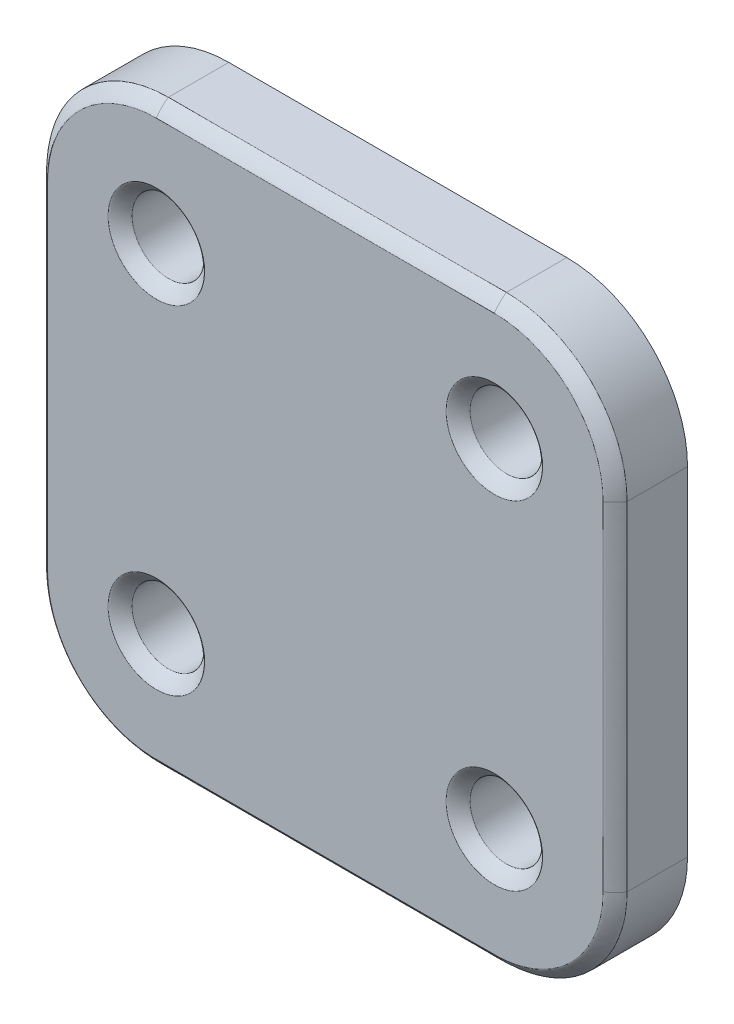
SolidWorks part; units mm, degrees
ref_plane "Plan de face" through (0, 0, 0) normal (0, 0, 1) x (1, 0, 0)
ref_plane "Plan de dessus" through (0, 0, 0) normal (0, 1, 0) x (1, 0, 0)
ref_plane "Plan de droite" through (0, 0, 0) normal (1, 0, 0) x (0, 0, -1)
sketch "Esquisse1" plane through (0, 0, 0) normal (0, 0, 1) x (1, 0, 0)
  line L0 (-7, 7) -> (7, 7) construction
  line L1 (7, -12) -> (-7, -12)
  line L2 (12, -7) -> (12, 7)
  line L3 (7, 12) -> (-7, 12)
  line L4 (-12, -7) -> (-12, 7)
  line L5 (12, -12) -> (-12, 12) construction
  line L6 (12, 12) -> (-12, -12) construction
  line L7 (-7, -7) -> (-7, 7) construction
  arc A0 (-7, -12) -> (-12, -7) centre (-7, -7) cw
  arc A1 (7, -12) -> (12, -7) centre (7, -7) ccw
  arc A2 (12, 7) -> (7, 12) centre (7, 7) ccw
  arc A3 (-7, 12) -> (-12, 7) centre (-7, 7) ccw
  circle A5 centre (-7, 7) radius 1.5
  circle A6 centre (7, 7) radius 1.5
  circle A7 centre (7, -7) radius 1.5
  circle A8 centre (-7, -7) radius 1.5
  point P0 (0, 0)
  dimension "D2" = 5
  dimension "D3" = 3
  dimension "D1" = 14
  dimension "D6" = 14
  dimension "D7" = 14
  dimension "D4" = 2
  dimension "D5" = 2
extrude "Boss.-Extru.1" add sketch "Esquisse1" along normal blind 3
fillet "Congé1" radius 0.5 12 edges at (-5.5, -7, 3) (8.5, -7, 3) (8.5, 7, 3) (-5.5, 7, 3) (-12, 0, 3) (-10.5355, 10.5355, 3) (0, 12, 3) (10.5355, 10.5355, 3) (12, 0, 3) (10.5355, -10.5355, 3) (0, -12, 3) (-10.5355, -10.5355, 3) conic rho 0.1
